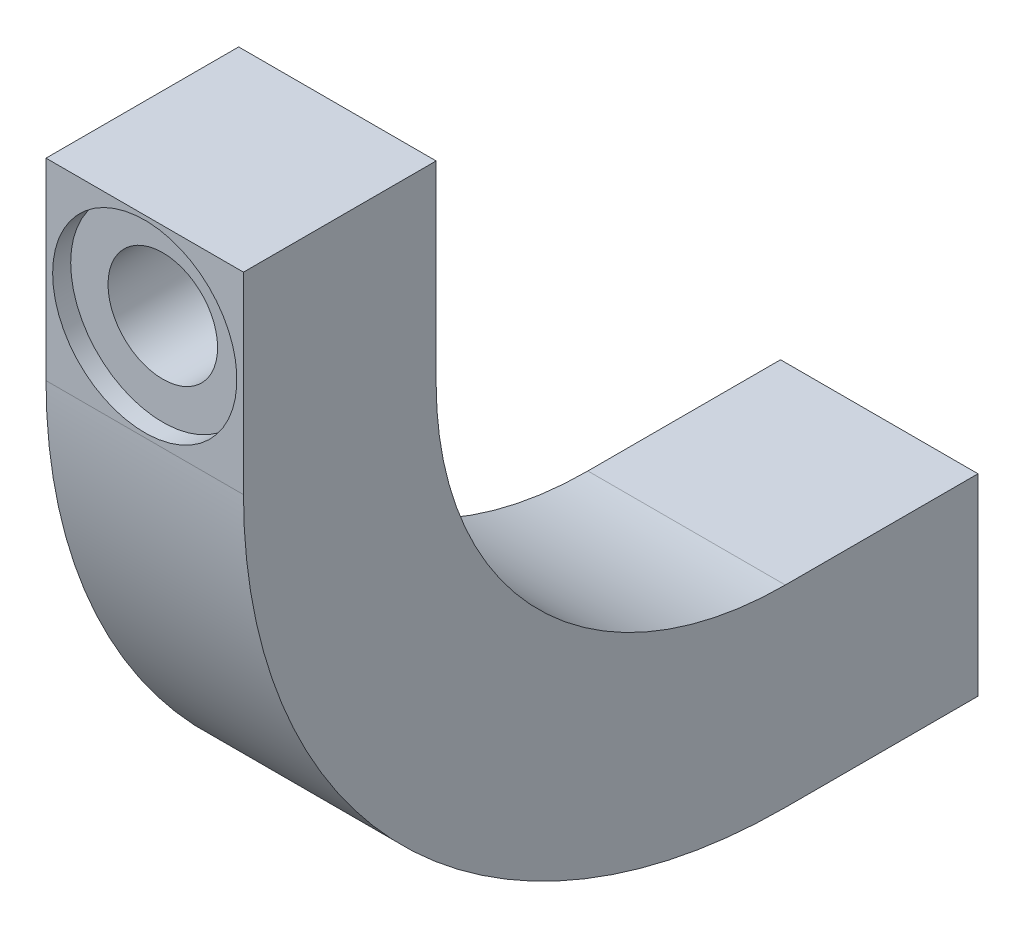
SolidWorks part; units mm, degrees
ref_plane "Front Plane" through (0, 0, 0) normal (0, 0, 1) x (1, 0, 0)
ref_plane "Top Plane" through (0, 0, 0) normal (0, 1, 0) x (1, 0, 0)
ref_plane "Right Plane" through (0, 0, 0) normal (1, 0, 0) x (0, 0, -1)
ref_axis "Z" through (0, 0, 22.75) along (0, 0, -1)
sketch "Sketch4" plane through (0, 0, 0) normal (0, 0, 1) x (1, 0, 0)
  circle A0 centre (0, 0) radius 17.5 construction
  dimension "D1" = 35
sketch "Sketch5" plane through (0, 0, 0) normal (1, 0, 0) x (0, 0, -1)
  line L0 (-18.5, 4) -> (-18.5, 0)
  line L1 (-18.5, 0) -> (-18.5, -4)
  line L2 (-26.5, -4) -> (-26.5, 4)
  line L6 (-26.5, 4) -> (-18.5, 4)
  line L12 (-22.75, 0) -> (-13.0351, 0) construction
  line L13 (0, 0) -> (-14.9091, -14.9091) construction
  line L14 (0, 0) -> (7.0065, 0) construction
  line L15 (0, -18.5) -> (-4, -18.5)
  line L16 (4, -18.5) -> (0, -18.5)
  line L17 (-4, -26.5) -> (4, -26.5)
  line L18 (4, -26.5) -> (4, -18.5)
  circle A0 centre (0, 0) radius 14 construction
  arc A1 (-18.5, -4) -> (-4, -18.5) centre (-4, -4) ccw
  arc A2 (-26.5, -4) -> (-4, -26.5) centre (-4, -4) ccw
  point P2 (9.4307, -21)
  point P4 (0, -2.1363)
  dimension "D1" = 28
  dimension "D4" = 4
  dimension "D2" = 45
  dimension "D3" = 8
  dimension "D5" = 18.5
sketch "Sketch6" plane through (0, 0, 0) normal (0, 1, 0) x (1, 0, 0)
  circle A0 centre (0, 0) radius 17.5 construction
  dimension "D1" = 35
extrude "Boss-Extrude1" add sketch "Sketch5" along normal blind 4.1 and the other way blind 4.1
sketch "Sketch7" plane through (0, 0, 0) normal (0, 0, 1) x (1, 0, 0)
  circle A0 centre (0, 0) radius 1.75
  dimension "D1" = 3.5
extrude "Cut-Extrude1" cut sketch "Sketch7" along normal through all
ref_axis "Y" through (0, -9.3489, 0) along (0, -1, 0)
sketch "Sketch12" plane through (0, 0, 26.5) normal (0, 0, 1) x (1, 0, 0)
  circle A0 centre (0, 0) radius 2.275
  dimension "D1" = 4.55
extrude "Cut-Extrude7" cut sketch "Sketch12" against normal blind 6
sketch "Sketch14" plane through (0, 0, 26.5) normal (0, 0, -1) x (1, 0, 0)
  circle A0 centre (0, 0) radius 3.825
  dimension "D1" = 7.65
extrude "Cut-Extrude10" cut sketch "Sketch14" along normal blind 0.75
sketch "Sketch16" plane through (0, 0, 0) normal (1, 0, 0) x (0, 0, -1)
  line L0 (0, -37.34) -> (0, 0) construction
  dimension "D1" = 37.34
ref_plane "Plane1" through (0, -37.34, 0) normal (0, 1, 0) x (1, 0, 0)
ref_axis "CX" through (0, -37.34, 4.4) along (0, 0, -1)
ref_plane "Plane2" through (0, 0, 0) normal (0, 0, -1) x (0, 1, 0)
ref_plane "Plane3" through (0, 0, 0) normal (1, 0, 0) x (0, 0, -1)
ref_axis "CZ" through (0, -8.7018, 0) along (0, -1, 0)
ref_axis "CY" through (-0.6471, -37.34, 0) along (1, 0, 0)
ref_point "CO"
sketch "Sketch15" plane through (0, -26.5, 0) normal (0, -1, 0) x (1, 0, 0)
  circle A0 centre (0, 0) radius 1.5
  dimension "D1" = 3
extrude "Cut-Extrude11" cut sketch "Sketch15" against normal blind 6
equation "\"rbracket-width\"= \"L2Thickness\" + 0.2"
equation "\"EyeCaptureRadius\"= ( \"EyeDiameter\" + \"EyeClearance\" ) / 2"
equation "\"rbracket_planetocenterline_dist\"= \"BasePlaneDistance\""
equation "\"EyeDiameter\" = 35"
equation "\"BasePlaneDistance\" = \"EyeDiameter\"/2+19.84"
equation "\"EyeClearance\" = 2"
equation "\"D1@Sketch4\"=\"EyeDiameter\""
equation "\"D1@Sketch6\"=\"EyeDiameter\""
equation "\"D1@Boss-Extrude1\"=\"rbracket-width\"/2"
equation "\"D2@Boss-Extrude1\"=\"rbracket-width\"/2"
equation "\"L2Thickness\" = 8"
equation "\"D3@Sketch5\"=\"L2Thickness\""
equation "\"D5@Sketch5\"=(\"EyeDiameter\"+\"EyeClearance\")/2"
equation "\"BearingThickness\"= 6"
equation "\"BearingOD\"=4.5"
equation "\"OuterBearingProudDistance\"= 0"
equation "\"D1@Cut-Extrude7\"=\"BearingThickness\"-\"OuterBearingProudDistance\""
equation "\"D1@Sketch12\"= \"BearingOD\" + \"PrinterFilamentThickness\" *\"ApplyPrinterOffset\" / 2"
equation "\"FlangeOD\"=7.5"
equation "\"FlangeThickness\"= 0.75"
equation "\"D1@Sketch14\"=\"FlangeOD\" + \"PrinterFilamentThickness\"*1.5 * \"ApplyPrinterOffset\""
equation "\"D1@Cut-Extrude10\"=\"FlangeThickness\""
equation "\"PrinterFilamentThickness\"= 0.1'For setting distances for things like pressfits"
equation "\"ApplyPrinterOffset\"= 1'Set to 0 for line-to-line. Set to 1 for applying guestimate dimensions to make the printer produce good parts"
equation "\"D1@Cut-Extrude11\"=3*1.5"
equation "\"D1@Sketch16\"=\"BasePlaneDistance\""
